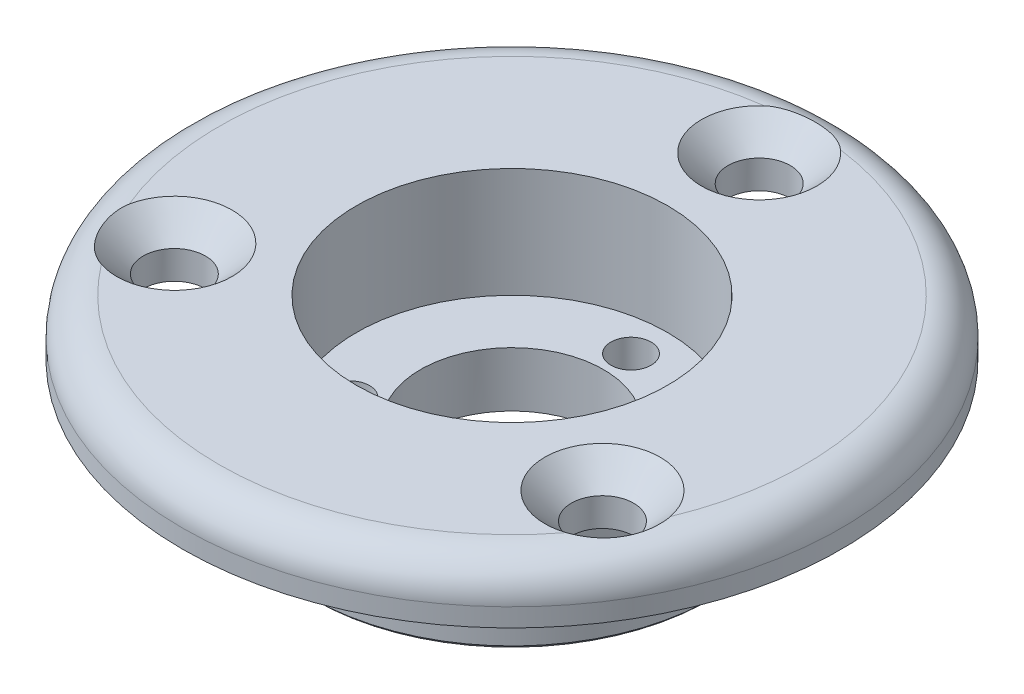
SolidWorks part; units mm, degrees
material "Alliage 1060"
ref_plane "Face" through (0, 0, 0) normal (0, 0, 1) x (1, 0, 0)
ref_plane "Dessus" through (0, 0, 0) normal (0, 1, 0) x (1, 0, 0)
ref_plane "Droite" through (0, 0, 0) normal (1, 0, 0) x (0, 0, -1)
sketch "Esquisse1" plane through (0, 0, 0) normal (1, 0, 0) x (0, 0, -1)
  line L0 (0, 0) -> (0, -70.5308) construction
  line L1 (-5, -3) -> (-5, 0)
  line L2 (-5, 0) -> (-8.5, 0)
  line L3 (-8.5, 0) -> (-8.5, 6)
  line L4 (-8.5, 6) -> (-18, 6)
  line L5 (-18, 6) -> (-18, 3)
  line L6 (-5, -3) -> (-11, -3)
  line L7 (-11, -3) -> (-11, 3)
  line L8 (-11, 3) -> (-18, 3)
  dimension "D1" = 17
  dimension "D2" = 3
  dimension "D3" = 36
  dimension "D4" = 9
  dimension "D5" = 10
  dimension "D6" = 22
  dimension "D7" = 6
revolve "Révolution1" add sketch "Esquisse1" angle 360 about L0
chamfer "Chanfrein1" distance 0.2 angle 45 1 edges at (0, -3, 11)
sketch "Esquisse4" plane through (0, 6, 0) normal (0, 1, 0) x (1, 0, 0)
  line L0 (0, 0) -> (0, 13.5) construction
  line L1 (0, 0) -> (-11.6913, -6.75) construction
  line L2 (0, 0) -> (11.6913, -6.75) construction
  circle A0 centre (0, 0) radius 13.5 construction
  circle A1 centre (0, 0) radius 6.5 construction
  dimension "D1" = 120
  dimension "D2" = 27
  dimension "D4" = 13
  dimension "D3" = 120
hole_wizard "Fraisage pour vis à tête fraisée M31" positions "Esquisse3D1" profile "Esquisse5" countersink size "M3" standard "Din" end condition through all
sketch3d "Esquisse3D1"
  point P0 (0, 6, -13.5)
  point P3 (11.6913, 6, 6.75)
  point P6 (-11.6913, 6, 6.75)
sketch "Esquisse5" plane through (0, 6, -13.5) normal (1, 0, 0) x (0, 0, 1)
  line L0 (0, 0) -> (0, 9)
  line L1 (0, 9) -> (1.7, 9)
  line L2 (1.7, 9) -> (1.7, 1.45)
  line L3 (1.7, 1.45) -> (3.15, 0)
  line L5 (3.15, 0) -> (0, 0)
  line L6 (-1.7, 1.45) -> (-3.15, 0) construction
  line L11 (0, -6.35) -> (0, 107.95) construction
  dimension "Diamètre du perçage jusqu'au prochain" = 3.4
  dimension "Profondeur du perçage jusqu'au prochain" = 9
  dimension "Diamètre du fraisage entrant" = 6.3
  dimension "Angle du fraisage entrant" = 90
fillet "Congé1" radius 2 1 edges at (0, 6, 18)
hole_wizard "Fraisage pour vis à tête fraisée M22" positions "Esquisse9" profile "Esquisse8" countersink size "M2" standard "Din" end condition through all
sketch "Esquisse9" plane through (0, -3, 0) normal (0, -1, 0) x (-1, 0, 0)
  line L0 (0, 0) -> (0, 13.5) construction
  line L1 (0, 0) -> (-11.6913, -6.75) construction
  line L2 (0, 0) -> (11.6913, -6.75) construction
  circle A0 centre (0, 0) radius 6.5 construction
  point P0 (0, 6.5)
  point P6 (-5.6292, -3.25)
  point P10 (5.6292, -3.25)
sketch "Esquisse8" plane through (0, -3, -6.5) normal (1, 0, 0) x (0, 0, -1)
  line L0 (0, 0) -> (0, 9.1962)
  line L1 (0, 9.1962) -> (1.1, 9.1962)
  line L2 (1.1, 9.1962) -> (1.1, 1.1)
  line L3 (1.1, 1.1) -> (2.2, 0)
  line L5 (2.2, 0) -> (0, 0)
  line L6 (-1.1, 1.1) -> (-2.2, 0) construction
  line L11 (0, -6.35) -> (0, 107.95) construction
  dimension "Diamètre du perçage jusqu'au prochain" = 2.2
  dimension "Profondeur du perçage jusqu'au prochain" = 9.1962
  dimension "Diamètre du fraisage entrant" = 4.4
  dimension "Angle du fraisage entrant" = 90
